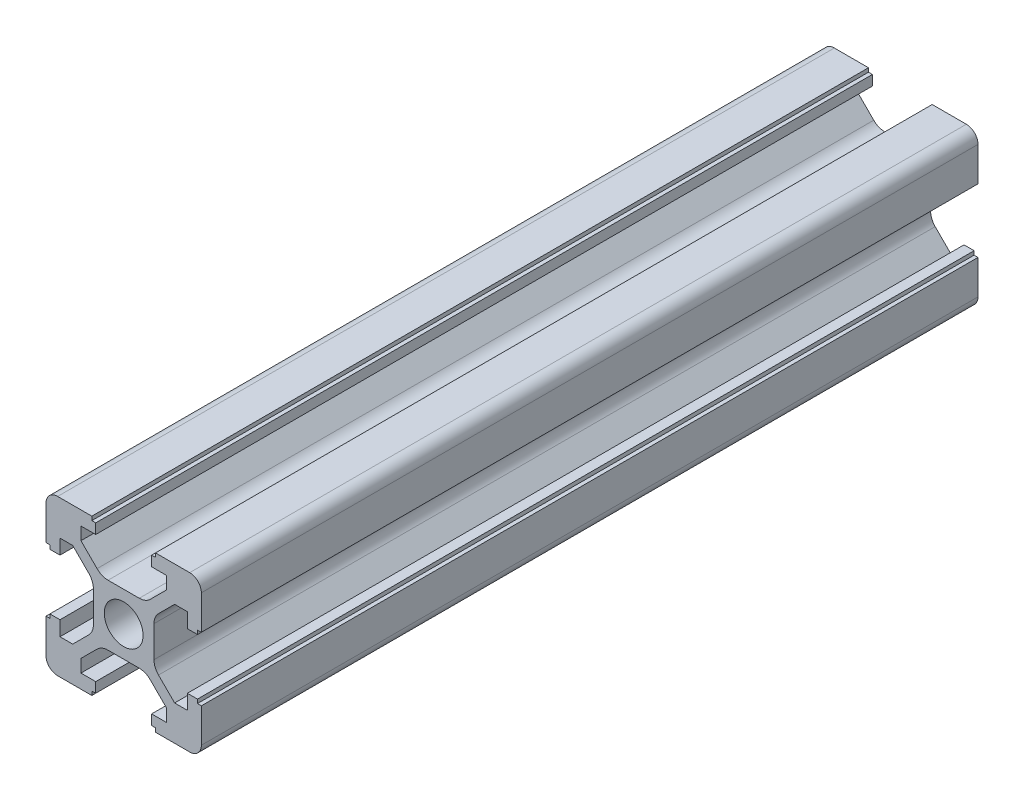
SolidWorks part; units mm, degrees
material "6063-O"
ref_plane "Front Plane" through (0, 0, 0) normal (0, 0, 1) x (1, 0, 0)
ref_plane "Top Plane" through (0, 0, 0) normal (0, 1, 0) x (1, 0, 0)
ref_plane "Right Plane" through (0, 0, 0) normal (1, 0, 0) x (0, 0, -1)
sketch "Sketch1" plane through (0, 0, 0) normal (0, 0, 1) x (1, 0, 0)
  line L0 (10, -4.1) -> (10, -8.5)
  line L1 (4.1, 10) -> (8.5, 10)
  line L2 (8.5, -10) -> (4.1, -10)
  line L3 (-8.5, -10) -> (-4.1, -10)
  line L4 (10, 8.5) -> (10, 4.1)
  line L7 (8.5, 10) -> (4.1, 10)
  line L8 (5.5, 6.5607) -> (3.4251, 4.4858)
  line L9 (8.5, 10) -> (4.1, 10)
  line L10 (3.9, 2.0109) -> (3.9, -2.0109)
  line L11 (2.0109, -3.9) -> (-2.0109, -3.9)
  line L12 (-3.9, -2.0109) -> (-3.9, 2.0109)
  line L13 (-2.0109, 3.9) -> (2.8393, 3.9)
  line L14 (2.5, 0) -> (22.2403, 0) construction
  line L15 (3.6, 9.5) -> (3.6, 8.2)
  line L16 (9.5, 3.6) -> (8.2, 3.6)
  line L17 (8.2, 3.6) -> (8.2, 5.5)
  line L18 (8.2, 5.5) -> (6.5607, 5.5)
  line L19 (10, -4.1) -> (10, -8.5)
  line L20 (4.1, 9.5) -> (3.6, 9.5)
  line L21 (4.1, 10) -> (4.1, 9.5)
  line L22 (8.5, 10) -> (4.1, 10)
  line L23 (10, 4.1) -> (9.5, 4.1)
  line L24 (9.5, 4.1) -> (9.5, 3.6)
  line L25 (5.5, 8.2) -> (5.5, 6.5607)
  line L26 (3.6, 8.2) -> (5.5, 8.2)
  line L27 (4.4858, 3.4251) -> (6.5607, 5.5)
  line L28 (10, -8.5) -> (10, -4.1)
  line L29 (6.5607, -5.5) -> (4.4858, -3.4251)
  line L30 (10, -8.5) -> (10, -4.1)
  line L31 (2.0109, -3.9) -> (-2.0109, -3.9)
  line L32 (3.9, 2.8393) -> (3.9, -2.0109)
  line L33 (9.5, -3.6) -> (8.2, -3.6)
  line L34 (3.6, -9.5) -> (3.6, -8.2)
  line L35 (3.6, -8.2) -> (5.5, -8.2)
  line L36 (5.5, -8.2) -> (5.5, -6.5607)
  line L37 (9.5, -4.1) -> (9.5, -3.6)
  line L38 (10, -4.1) -> (9.5, -4.1)
  line L39 (10, -8.5) -> (10, -4.1)
  line L40 (4.1, -10) -> (4.1, -9.5)
  line L41 (4.1, -9.5) -> (3.6, -9.5)
  line L42 (8.2, -5.5) -> (6.5607, -5.5)
  line L43 (8.2, -3.6) -> (8.2, -5.5)
  line L44 (3.4251, -4.4858) -> (5.5, -6.5607)
  line L45 (-4.1, -10) -> (-8.5, -10)
  line L46 (-10, -8.5) -> (-10, -4.1)
  line L47 (-8.5, -10) -> (-4.1, -10)
  line L48 (-5.5, -6.5607) -> (-3.4251, -4.4858)
  line L49 (-8.5, -10) -> (-4.1, -10)
  line L50 (-3.9, -2.0109) -> (-3.9, 2.0109)
  line L51 (2.0109, -3.9) -> (-2.0109, -3.9)
  line L52 (-3.6, -9.5) -> (-3.6, -8.2)
  line L53 (-9.5, -3.6) -> (-8.2, -3.6)
  line L54 (-8.2, -3.6) -> (-8.2, -5.5)
  line L55 (-8.2, -5.5) -> (-6.5607, -5.5)
  line L56 (-4.1, -9.5) -> (-3.6, -9.5)
  line L57 (-4.1, -10) -> (-4.1, -9.5)
  line L58 (-8.5, -10) -> (-4.1, -10)
  line L59 (-10, -4.1) -> (-9.5, -4.1)
  line L60 (-9.5, -4.1) -> (-9.5, -3.6)
  line L61 (-5.5, -8.2) -> (-5.5, -6.5607)
  line L62 (-3.6, -8.2) -> (-5.5, -8.2)
  line L63 (-4.4858, -3.4251) -> (-6.5607, -5.5)
  line L64 (-10, 4.1) -> (-10, 8.5)
  line L65 (-8.5, 10) -> (-4.1, 10)
  line L66 (-10, 8.5) -> (-10, 4.1)
  line L67 (-6.5607, 5.5) -> (-4.4858, 3.4251)
  line L68 (-10, 8.5) -> (-10, 4.1)
  line L69 (-2.0109, 3.9) -> (2.0109, 3.9)
  line L70 (-3.9, -2.0109) -> (-3.9, 2.0109)
  line L71 (-9.5, 3.6) -> (-8.2, 3.6)
  line L72 (-3.6, 9.5) -> (-3.6, 8.2)
  line L73 (-3.6, 8.2) -> (-5.5, 8.2)
  line L74 (-5.5, 8.2) -> (-5.5, 6.5607)
  line L75 (-9.5, 4.1) -> (-9.5, 3.6)
  line L76 (-10, 4.1) -> (-9.5, 4.1)
  line L77 (-10, 8.5) -> (-10, 4.1)
  line L78 (-4.1, 10) -> (-4.1, 9.5)
  line L79 (-4.1, 9.5) -> (-3.6, 9.5)
  line L80 (-8.2, 5.5) -> (-6.5607, 5.5)
  line L81 (-8.2, 3.6) -> (-8.2, 5.5)
  line L82 (-3.4251, 4.4858) -> (-5.5, 6.5607)
  line L83 (4.1, -10) -> (8.5, -10)
  arc A0 (2.0109, -3.9) -> (3.4251, -4.4858) centre (2.0109, -5.9) cw
  arc A1 (4.4858, -3.4251) -> (3.9, -2.0109) centre (5.9, -2.0109) cw
  arc A2 (3.9, 2.0109) -> (4.4858, 3.4251) centre (5.9, 2.0109) cw
  arc A3 (2.0109, 3.9) -> (3.4251, 4.4858) centre (2.0109, 5.9) ccw
  arc A4 (-2.0109, 3.9) -> (-3.4251, 4.4858) centre (-2.0109, 5.9) cw
  arc A5 (-4.4858, 3.4251) -> (-3.9, 2.0109) centre (-5.9, 2.0109) cw
  arc A6 (-3.4251, -4.4858) -> (-2.0109, -3.9) centre (-2.0109, -5.9) cw
  arc A7 (-3.9, -2.0109) -> (-4.4858, -3.4251) centre (-5.9, -2.0109) cw
  circle A8 centre (0, 0) radius 2.5
  arc A9 (-8.5, -10) -> (-10, -8.5) centre (-8.5, -8.5) cw
  arc A10 (-10, 8.5) -> (-8.5, 10) centre (-8.5, 8.5) cw
  arc A11 (8.5, 10) -> (10, 8.5) centre (8.5, 8.5) cw
  arc A12 (8.5, -10) -> (10, -8.5) centre (8.5, -8.5) ccw
  point P0 (0, 0)
  point P86 (0, 0)
  point P107 (10, -10)
  dimension "D3" = 2
  dimension "D5" = 5
  dimension "D2" = 1.5
  dimension "D8" = 1.5
  dimension "D6" = 4
  dimension "D7" = 6.1
  dimension "D11" = 0.5
  dimension "D12" = 0.5
extrude "Boss-Extrude2" add sketch "Sketch1" along normal blind 100 contours L2 A12 L0 L38 L37 L33 L43 L42 L29 A1 L10 A2 L27 L18 L17 L16 L24 L23 L4 A11 L1 L21 L20 L15 L26 L25 L8 A3 L13 A4 L82 L74 L73 L72 L79 L78 L65 A10 L64 L76 L75 L71 L81 L80 L67 A5 L12 region at (9.7172, -6.3, 0)
